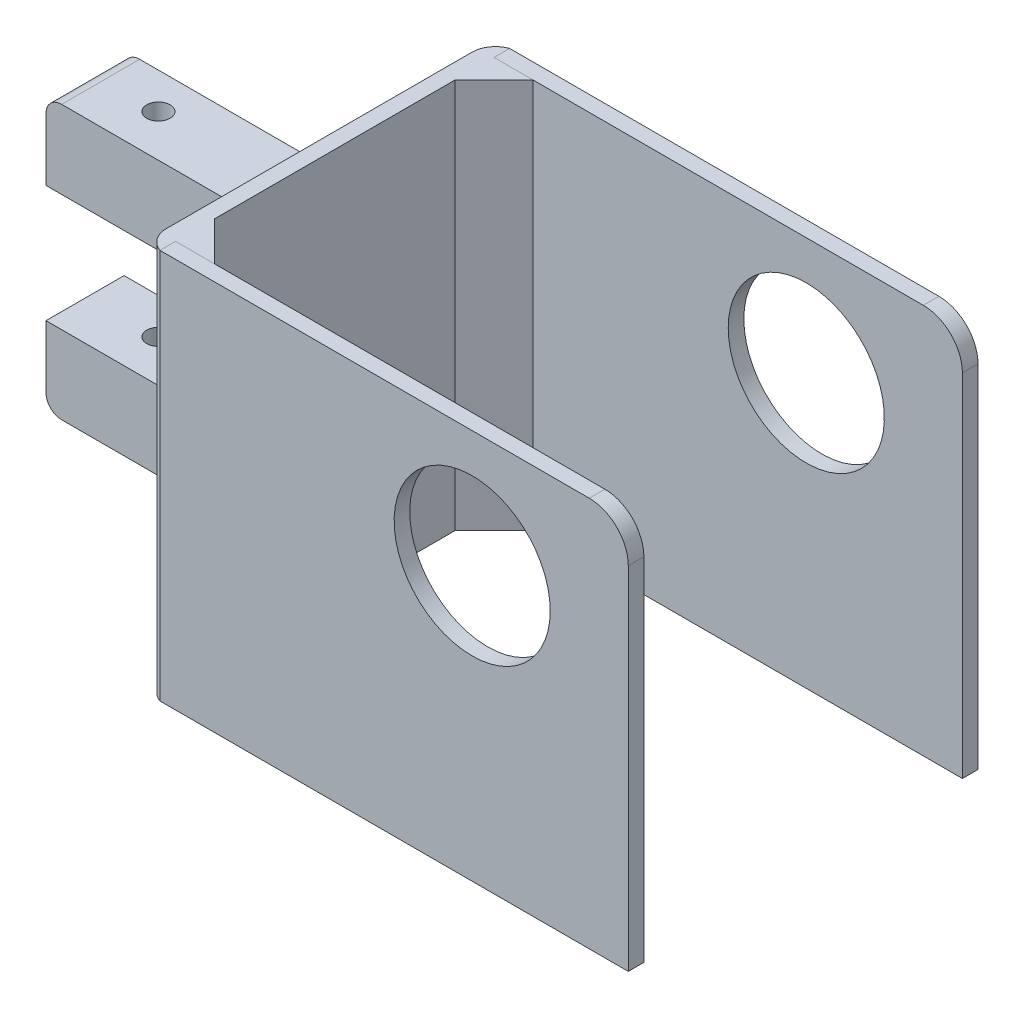
SolidWorks part; units mm, degrees
ref_plane "前视基准面" through (0, 0, 0) normal (0, 0, 1) x (1, 0, 0)
ref_plane "上视基准面" through (0, 0, 0) normal (0, 1, 0) x (1, 0, 0)
ref_plane "右视基准面" through (0, 0, 0) normal (1, 0, 0) x (0, 0, -1)
sketch "草图3" plane through (0, 0, 0) normal (0, 0, 1) x (1, 0, 0)
  line L0 (60.2665, 6.5325) -> (60.2665, 16.5325)
  line L1 (10.7665, 16.5325) -> (10.7665, 6.5325)
  line L2 (10.7665, 16.5325) -> (60.2665, 16.5325)
  circle A0 centre (60.2665, 16.5325) radius 3
  circle A1 centre (60.2665, 6.5325) radius 3
  circle A6 centre (10.7665, 6.5325) radius 3
  circle A7 centre (10.7665, 16.5325) radius 3
  dimension "D1" = 6
  dimension "D2" = 6
  dimension "D4" = 6
  dimension "D5" = 6
  dimension "D3" = 10
  dimension "D6" = 49.5
  dimension "D7" = 49.5
  dimension "D8" = 10
extrude "凸台-拉伸6" add sketch "草图3" along normal blind 0.001 contours A6 | A0 | A1 | A7
sketch "草图11" plane through (0, 0, 0.001) normal (0, 0, 1) x (1, 0, 0)
  circle A0 centre (10.7665, 16.5325) radius 2.25
  circle A1 centre (10.7665, 6.5325) radius 2.25
  circle A2 centre (60.2665, 16.5325) radius 2.25
  circle A3 centre (60.2665, 6.5325) radius 2.25
  dimension "D1" = 4.5
  dimension "D2" = 4.5
  dimension "D3" = 4.5
  dimension "D4" = 4.5
extrude "切除-拉伸2" cut sketch "草图11" against normal through all both and the other way through all
sketch "草图12" plane through (0, 0, 0.001) normal (0, 0, 1) x (1, 0, 0)
  line L4 (10.7665, 16.5325) -> (60.2665, 6.5325) construction
  line L5 (10.7665, 6.5325) -> (60.2665, 16.5325) construction
  line L6 (60.2665, 16.5325) -> (60.2665, 6.5325) construction
  line L7 (5.5165, 26.5325) -> (65.5165, 26.5325)
  line L8 (5.5165, 26.5325) -> (5.5165, 1.5325)
  line L9 (5.5165, -23.4675) -> (65.5165, -23.4675)
  line L10 (65.5165, 26.5325) -> (65.5165, -23.4675)
  line L11 (5.5165, 1.5325) -> (5.5165, -23.4675) construction
  line L13 (5.5165, -23.4675) -> (5.5165, 1.5325) construction
  line L16 (5.5165, 1.5325) -> (5.5165, -23.4675)
  circle A4 centre (45.5165, 11.5325) radius 10
  point P8 (35.5165, 11.5325)
  point P9 (35.5165, 26.5325)
  point P10 (-46.6091, 14.6442)
  point P11 (60.2665, 11.5325)
  dimension "D5" = 20
  dimension "D1" = 60
  dimension "D2" = 50
  dimension "D3" = 15
  dimension "D4" = 14.75
extrude "凸台-拉伸7" add sketch "草图12" along normal blind 2 and the other way blind 0.8019 contours L7 L10 L9 L16 L8
sketch "草图14" plane through (0, 0, -0.8009) normal (0, 0, -1) x (-1, 0, 0)
  line L0 (-60.2665, 16.5325) -> (-60.2665, 6.5325) construction
  circle A8 centre (-45.5165, 11.5325) radius 10
  point P14 (-60.2665, 11.5325)
  point P15 (0.1696, -0.033)
  dimension "D2" = 20
extrude "切除-拉伸3" cut sketch "草图14" against normal blind 3
sketch "草图15" plane through (0, 0, -0.8009) normal (0, 0, -1) x (-1, 0, 0)
  circle A0 centre (-45.5165, 11.5325) radius 10 construction
  circle A1 centre (-45.5165, 11.5325) radius 10
  circle A2 centre (-45.5165, -12.4675) radius 2.75
  dimension "D2" = 5.5
  dimension "D1" = 24
extrude "凸台-拉伸10" add sketch "草图12<4>" along normal blind 44
sketch "草图12<4>" plane through (0, 0, 0.001) normal (0, 0, 1) x (1, 0, 0) same geometry as "草图12"
sketch "草图19" plane through (65.5165, 0, 0) normal (1, 0, 0) x (0, 0, -1)
  line L0 (-44.001, 26.5325) -> (-42.001, 26.5325)
  line L1 (-44.001, 26.5325) -> (0.8009, 26.5325) construction
  line L2 (0.8009, 26.5325) -> (-1.1991, 26.5325)
  dimension "D1" = 2
  dimension "D2" = 2
sketch "草图20" plane through (65.5165, 0, 0) normal (1, 0, 0) x (0, 0, -1)
  line L0 (-42.001, 26.5325) -> (-42.001, -23.4675)
  line L1 (-44.001, -23.4675) -> (0.8009, -23.4675) construction
  line L2 (-42.001, 26.5325) -> (-1.1991, 26.5325)
  line L3 (-1.1991, 26.5325) -> (-1.1991, -23.4675)
  line L4 (-1.1991, -23.4675) -> (-42.001, -23.4675)
extrude "切除-拉伸6" cut sketch "草图20" against normal blind 60
sketch "草图21" plane through (5.5165, 0, 0) normal (-1, 0, 0) x (0, 0, 1)
  line L0 (-0.8009, -23.4675) -> (44.001, -23.4675)
  line L1 (44.001, -23.4675) -> (44.001, 26.5325)
  line L2 (44.001, 26.5325) -> (-0.8009, 26.5325)
  line L3 (-0.8009, 26.5325) -> (-0.8009, -23.4675)
extrude "凸台-拉伸11" add sketch "草图21" along normal blind 2
sketch "草图25" plane through (0, 0, -0.8009) normal (0, 0, -1) x (-1, 0, 0)
  circle A0 centre (-33.0165, 19.0325) radius 0.75
  circle A2 centre (-33.0165, 4.0325) radius 0.75
  circle A3 centre (-18.0165, 19.0325) radius 0.75
  circle A4 centre (-18.0165, 3.623) radius 0.75
  circle A5 centre (-25.5165, 19.0325) radius 0.75
  circle A6 centre (-25.5165, 3.8277) radius 0.75
  circle A7 centre (-18.0165, 11.3277) radius 0.75
  dimension "D4" = 15
  dimension "D5" = 1.5
  dimension "D1" = 1.5
  dimension "D2" = 1.5
  dimension "D3" = 1.5
  dimension "D6" = 1.5
  dimension "D7" = 1.5
  dimension "D8" = 1.5
fillet "圆角2" radius 5 1 edges at (65.5165, 26.5325, 0.1991)
fillet "圆角3" radius 5 1 edges at (65.5165, 26.5325, 43.001)
fillet "圆角5" radius 3 1 edges at (3.5165, 1.5325, 44.001)
fillet "圆角6" radius 3 1 edges at (3.5165, 1.5325, -0.8009)
sketch "草图26" plane through (0, 0, -0.8009) normal (0, 0, -1) x (-1, 0, 0)
  circle A0 centre (-24.5861, -9.3979) radius 2.75
  dimension "D1" = 5.5
  dimension "D2" = 29.6
sketch "草图29" plane through (0, 0, -0.8009) normal (0, 0, -1) x (-1, 0, 0)
  line L0 (-65.5165, 21.5325) -> (-65.5165, -23.4675) construction
  line L1 (-65.5165, 4.1055) -> (-35.5165, -23.4675)
  line L2 (-5.5165, -23.4675) -> (-65.5165, -23.4675) construction
  line L3 (-35.5165, -23.4675) -> (-65.5165, -23.4675)
  line L4 (-65.5165, -23.4675) -> (-65.5165, 4.1055)
sketch "草图35" plane through (0, -23.4675, 0) normal (0, -1, 0) x (1, 0, 0)
  line L0 (5.5165, 42.001) -> (10.5165, 42.001)
  line L1 (5.5165, 42.001) -> (65.5165, 42.001) construction
  line L2 (10.5165, 42.001) -> (5.5165, 37.001)
  line L3 (5.5165, -0.8009) -> (5.5165, 44.001) construction
  line L4 (5.5165, 37.001) -> (5.5165, 42.001)
  line L5 (5.5165, 1.1991) -> (5.5165, 6.1991)
  line L6 (5.5165, 6.1991) -> (10.5165, 1.1991)
  line L7 (5.5165, 1.1991) -> (65.5165, 1.1991) construction
  line L8 (10.5165, 1.1991) -> (5.5165, 1.1991)
  dimension "D1" = 5
  dimension "D2" = 5
  dimension "D3" = 5
  dimension "D4" = 5
extrude "凸台-拉伸15" add sketch "草图35" against normal blind 50
sketch "草图36" plane through (3.5165, 0, 0) normal (-1, 0, 0) x (0, 0, 1)
  line L0 (2.0275, 1.5325) -> (41.1726, 1.5325) construction
  line L1 (16.6, -15.9675) -> (26.6, -15.9675)
  line L2 (16.6, -15.9675) -> (16.6, 19.0325)
  line L3 (16.6, 19.0325) -> (26.6, 19.0325)
  line L4 (26.6, -15.9675) -> (26.6, 19.0325)
  line L5 (16.6, -15.9675) -> (26.6, 19.0325) construction
  line L6 (16.6, 19.0325) -> (26.6, -15.9675) construction
  point P0 (21.6, 1.5325)
  dimension "D1" = 35
  dimension "D2" = 10
extrude "凸台-拉伸16" add sketch "草图36" along normal blind 30
fillet "圆角7" radius 2 2 edges at (-26.4835, -15.9675, 21.6) (-26.4835, 19.0325, 21.6)
sketch "草图38" plane through (-26.4835, 0, 0) normal (-1, 0, 0) x (0, 0, 1)
  line L0 (16.6, 9.0325) -> (16.6, -5.9675)
  line L1 (16.6, 17.0325) -> (16.6, -13.9675) construction
  line L2 (16.6, -5.9675) -> (26.6, -5.9675)
  line L3 (26.6, -13.9675) -> (26.6, 17.0325) construction
  line L4 (26.6, -5.9675) -> (26.6, 9.0325)
  line L5 (26.6, 9.0325) -> (16.6, 9.0325)
  point P0 (26.6, 1.5325)
  point P5 (16.6, 1.5325)
  dimension "D1" = 7.5
sketch "草图39" plane through (0, 19.0325, 0) normal (0, 1, 0) x (1, 0, 0)
  line L0 (-24.4835, -16.6) -> (-24.4835, -26.6) construction
  circle A0 centre (-17.4835, -21.1984) radius 1.5
  dimension "D2" = 3
  dimension "D1" = 7
extrude "切除-拉伸8" cut sketch "草图39" against normal through all both and the other way through all contours A0
extrude "切除-拉伸9" cut sketch "草图38" against normal blind 15
